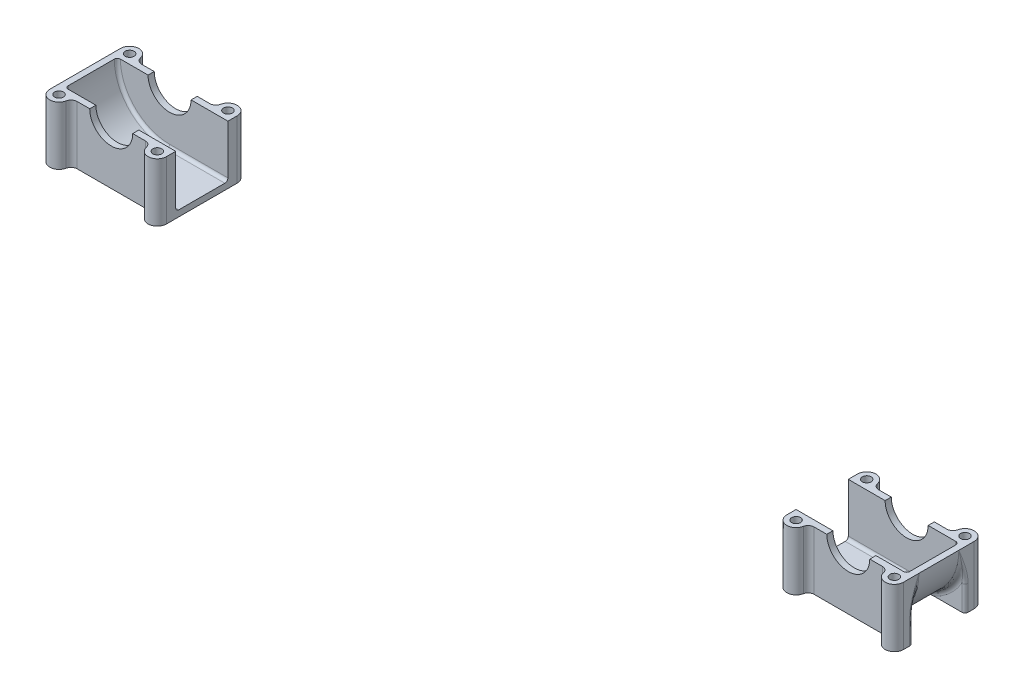
SolidWorks part; units mm, degrees
material "6061-T6 (SS)"
ref_plane "Front" through (0, 0, 0) normal (0, 0, 1) x (1, 0, 0)
ref_plane "Top" through (0, 0, 0) normal (0, 1, 0) x (1, 0, 0)
ref_plane "Right" through (0, 0, 0) normal (1, 0, 0) x (0, 0, -1)
sketch "Sketch1" plane through (0, 0, 0) normal (0, 0, 1) x (1, 0, 0)
  line L0 (-30.1625, 0) -> (30.1625, 0)
  line L1 (-30.1625, 0) -> (-30.1625, -30.1625)
  line L2 (-30.1625, -30.1625) -> (30.1625, -30.1625)
  line L3 (30.1625, -30.1625) -> (30.1625, 0)
  line L4 (0, -26.9875) -> (30.1625, -26.9875)
  arc A0 (-26.9875, 0) -> (26.9875, 0) centre (0, 0) ccw
  arc A1 (-11.1125, 0) -> (11.1125, 0) centre (0, 0) ccw
  arc A2 (-30.1625, 0) -> (30.1625, 0) centre (0, 0) ccw
  circle A3 centre (0, 0) radius 30.1625 construction
  circle A4 centre (0, 0) radius 26.9875 construction
  dimension "D1" = 53.975
  dimension "D2" = 22.225
  dimension "D4" = 30.1625
  dimension "D3" = 3.175
extrude "Boss-Extrude1" add sketch "Sketch1" along normal mid plane 26.9875 contours L0 A2 L4 A0 | A2 L2 L3 L4 region at (-28.575, -0.5304, 0) region at (19.3844, -28.7092, 0)
extrude "Boss-Extrude2" add sketch "Sketch1<3>" against normal blind 3.175 from surface contours A2 L1 L2 | L0 A2 L4 A0 | A2 L2 L3 L4 | A2 L4 L3 | L4 A2 L0 A0 | A1 L0 A0 region at (-23.4252, -23.4252, 0) region at (-28.575, -0.5304, 0) region at (0, -12.8294, 0) region at (19.3844, -28.7092, 0) region at (19.3692, -19.3692, 0) region at (25.5334, -20.6683, 0) starting at face at (-1.4435, -21.0227, -13.4937)
sketch "Sketch1<3>" plane through (0, 0, 0) normal (0, 0, 1) x (1, 0, 0) same geometry as "Sketch1"
extrude "Boss-Extrude3" add sketch "Sketch1<4>" along normal blind 3.175 from surface contours A2 L1 L2 | L0 A2 L4 A0 | A2 L2 L3 L4 | A2 L4 L3 | L4 A2 L0 A0 | A1 L0 A0 region at (-23.4252, -23.4252, 0) region at (-28.575, -0.5304, 0) region at (0, -12.8294, 0) region at (19.3844, -28.7092, 0) region at (19.3692, -19.3692, 0) region at (25.5334, -20.6683, 0) starting at face at (-1.4435, -21.0227, 13.4937)
sketch "Sketch1<4>" plane through (0, 0, 0) normal (0, 0, 1) x (1, 0, 0) same geometry as "Sketch1"
sketch "Sketch2" plane through (0, -30.1625, 0) normal (0, -1, 0) x (1, 0, 0)
  line L5 (-30.1625, 18.2562) -> (-30.1625, -18.2563)
  line L6 (-20.6375, -18.2563) -> (-20.6375, 18.2562)
  line L7 (20.6375, 18.2562) -> (20.6375, -18.2563)
  line L8 (30.1625, -18.2563) -> (30.1625, 18.2562)
  line L9 (0, 13.4937) -> (0, -13.4937)
  line L10 (-30.1625, -16.6687) -> (30.1625, -16.6687)
  line L12 (30.1625, 16.6687) -> (-30.1625, 16.6687)
  line L16 (30.1625, 16.6687) -> (-30.1625, 16.6687)
  line L17 (11.1125, -13.4937) -> (-11.1125, -13.4937) construction
  line L18 (-11.1125, 13.4937) -> (11.1125, 13.4937) construction
  line L19 (11.1125, -13.4937) -> (-11.1125, -13.4937)
  line L20 (-11.1125, 13.4937) -> (11.1125, 13.4937)
  line L21 (30.1625, -16.6687) -> (30.1625, 16.6687)
  line L22 (30.1625, -16.6687) -> (30.1625, 16.6687)
  line L27 (0, 13.4937) -> (0, -13.4937)
  line L29 (-30.1625, 13.4937) -> (0, 13.4937)
  line L31 (-30.1625, 13.4937) -> (0, 13.4937)
  line L33 (0, -13.4937) -> (-30.1625, -13.4937)
  line L35 (0, -13.4937) -> (-30.1625, -13.4937)
  line L36 (-30.1625, -13.4937) -> (-30.1625, -16.6687)
  line L37 (-30.1625, -16.6687) -> (30.1625, -16.6687)
  line L38 (-30.1625, -13.4937) -> (-30.1625, -16.6687)
  line L39 (-30.1625, 16.6687) -> (-30.1625, 13.4937)
  line L40 (-30.1625, 16.6687) -> (-30.1625, 13.4937)
  circle A0 centre (-25.4, 18.2562) radius 4.7625
  circle A1 centre (25.4, 18.2562) radius 4.7625
  circle A2 centre (-25.4, -18.2563) radius 4.7625
  circle A3 centre (25.4, -18.2563) radius 4.7625
  circle A4 centre (-25.4, 18.2562) radius 2.286
  circle A5 centre (25.4, 18.2562) radius 2.286
  circle A6 centre (25.4, -18.2563) radius 2.286
  circle A7 centre (-25.4, -18.2563) radius 2.286
  line M6 (-30.1625, -16.6687) -> (30.1625, -16.6687)
  line M8 (30.1625, 16.6687) -> (-30.1625, 16.6687)
  dimension "D1" = 9.525
  dimension "D5" = 4.572
  dimension "D2" = 0
extrude "Boss-Extrude4" add sketch "Sketch2" against normal up to surface (30.1625 mm away) contours A0 L5 M8 | A1 L8 M8 | A3 L8 M6 | A2 L5 M6 | A0 | A2 | A3 | A1 region at (-30.0812, -30.1625, 17.0633) region at (-30.0812, -30.1625, -17.0633) region at (30.0812, -30.1625, 17.0633) region at (30.0812, -30.1625, -17.0633) up to face at (-21.9075, 0, 0)
fillet "Fillet3" radius 1.5875 4 edges at (-19.083, -19.083, 13.4937) (15.0812, -26.9875, -13.4937) (15.0812, -26.9875, 13.4937) (-19.083, -19.083, -13.4937)
extrude "Cut-Extrude1" cut sketch "Sketch2<3>" against normal through all both and the other way through all contours A4 | A5 | A6 | A7
sketch "Sketch2<3>" plane through (0, -30.1625, 0) normal (0, -1, 0) x (1, 0, 0) same geometry as "Sketch2"
fillet "Fillet7" radius 3.175 4 edges at (20.9099, -15.0812, -16.6687) (-20.9099, -15.0812, -16.6687) (20.9099, -15.0812, 16.6687) (-20.9099, -15.0812, 16.6687)
ref_plane "Plane1" through (190.5, 0, 0) normal (1, 0, 0) x (0, 0, -1)
fillet "Fillet11" radius 3.175 2 edges at (-21.3281, -21.3281, 13.4937) (-21.3281, -21.3281, -13.4937)
fillet "Fillet12" radius 1.5875 4 edges at (-30.1625, -7.849, 12.636) (-30.1625, -7.849, -12.636) (-30.1625, -22.1808, 13.4937) (-30.1625, -22.1808, -13.4937)
mirror "Mirror5" about plane through (190.5, 0, 0) normal (1, 0, 0) of bodies 106
